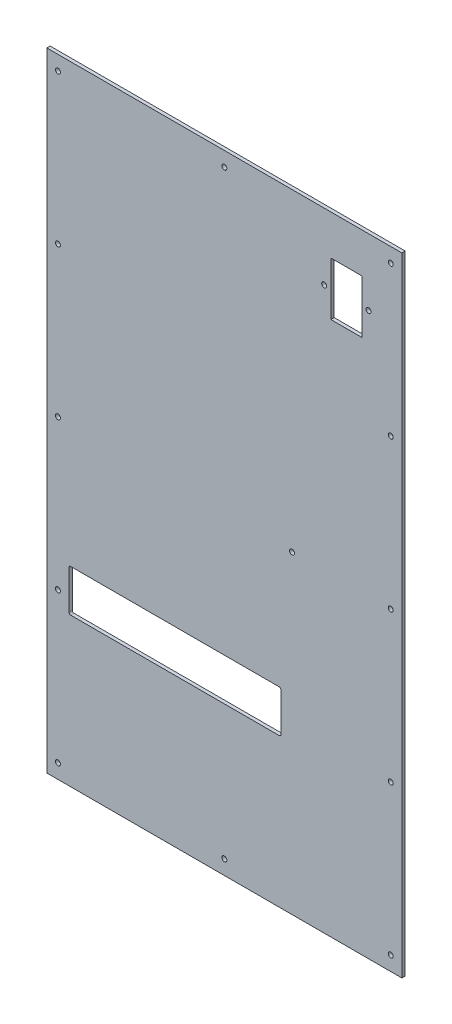
SolidWorks part; units mm, degrees
ref_plane "Спереди" through (0, 0, 0) normal (0, 0, 1) x (1, 0, 0)
ref_plane "Сверху" through (0, 0, 0) normal (0, 1, 0) x (1, 0, 0)
ref_plane "Справа" through (0, 0, 0) normal (1, 0, 0) x (0, 0, -1)
sketch "Эскиз1" plane through (0, 0, 0) normal (0, 0, 1) x (1, 0, 0)
  line L0 (0, 0) -> (320, 0)
  line L1 (0, 0) -> (0, 566)
  line L2 (320, 0) -> (320, 566)
  line L3 (0, 566) -> (320, 566)
  line L4 (10, 553) -> (310, 553) construction
  line L5 (10, 553) -> (10, 13) construction
  line L6 (310, 553) -> (310, 13) construction
  line L7 (10, 13) -> (310, 13) construction
  line L8 (160, 553) -> (160, 13) construction
  circle A0 centre (10, 553) radius 2.25
  circle A1 centre (10, 418) radius 2.25
  circle A2 centre (10, 283) radius 2.25
  circle A3 centre (10, 148) radius 2.25
  circle A4 centre (10, 13) radius 2.25
  circle A5 centre (310, 13) radius 2.25
  circle A6 centre (160, 553) radius 2.25
  circle A7 centre (310, 553) radius 2.25
  circle A8 centre (310, 418) radius 2.25
  circle A9 centre (310, 283) radius 2.25
  circle A10 centre (310, 148) radius 2.25
  circle A11 centre (160, 13) radius 2.25
  dimension "D7" = 4.5
  dimension "D9" = 135
  dimension "D10" = 4.5
  dimension "D12" = 135
  dimension "D13" = 4.5
  dimension "D14" = 4.5
  dimension "D1" = 566
  dimension "D2" = 320
  dimension "D3" = 10
  dimension "D4" = 13
  dimension "D5" = 10
  dimension "D6" = 13
  dimension "D8" = 5
  dimension "D11" = 5
extrude "Бобышка-Вытянуть1" add sketch "Эскиз1" along normal blind 3
sketch "Эскиз2" plane through (0, 0, 0) normal (0, 0, -1) x (-1, 0, 0)
  line L0 (-34.5, 497.8788) -> (-34.5, 452.1212) construction
  line L1 (-50.3712, 513.75) -> (-96.1288, 513.75) construction
  line L2 (-50.3712, 436.25) -> (-96.1288, 436.25) construction
  line L3 (-112, 497.8788) -> (-112, 452.1212) construction
  line L4 (-34.5, 497.8788) -> (-34.5, 452.1212) construction
  line L5 (-50.3712, 513.75) -> (-96.1288, 513.75) construction
  line L6 (-50.3712, 436.25) -> (-96.1288, 436.25) construction
  line L7 (-112, 497.8788) -> (-112, 452.1212) construction
  line L8 (-155.25, 500.5) -> (-124.75, 500.5) construction
  line L9 (-124.75, 475.5) -> (-155.25, 475.5) construction
  line L10 (-155.25, 500.5) -> (-124.75, 500.5) construction
  line L11 (-124.75, 475.5) -> (-155.25, 475.5) construction
  line L16 (-130, 446) -> (-130, 461)
  line L17 (-151, 446) -> (-130, 446)
  line L18 (-151, 461) -> (-151, 446)
  line L19 (-130, 461) -> (-151, 461)
  line L20 (-130, 446) -> (-130, 461) construction
  line L21 (-151, 446) -> (-130, 446) construction
  line L22 (-151, 461) -> (-151, 446) construction
  line L23 (-130, 461) -> (-151, 461) construction
  line L24 (-50.3712, 513.75) -> (-149.75, 513.75)
  line L25 (-149.75, 513.75) -> (-167.5, 496)
  line L26 (-167.5, 496) -> (-167.5, 454)
  line L27 (-157.5, 444) -> (-112.25, 444)
  line L28 (-112.25, 444) -> (-104.5, 436.25)
  line L29 (-104.5, 436.25) -> (-50.3712, 436.25)
  line L30 (-34.5, 452.1212) -> (-34.5, 497.8788)
  line L31 (-167.5, 454) -> (-157.5, 444)
  line L32 (-50.3712, 513.75) -> (-34.5, 497.8788)
  line L33 (-34.5, 452.1212) -> (-50.3712, 436.25)
  arc A0 (-50.3712, 436.25) -> (-34.5, 452.1212) centre (-73.25, 475) ccw construction
  arc A1 (-34.5, 497.8788) -> (-50.3712, 513.75) centre (-73.25, 475) ccw construction
  arc A2 (-112, 452.1212) -> (-96.1288, 436.25) centre (-73.25, 475) ccw construction
  arc A3 (-96.1288, 513.75) -> (-112, 497.8788) centre (-73.25, 475) ccw construction
  arc A4 (-50.3712, 436.25) -> (-34.5, 452.1212) centre (-73.25, 475) ccw construction
  arc A5 (-34.5, 497.8788) -> (-50.3712, 513.75) centre (-73.25, 475) ccw construction
  arc A6 (-112, 452.1212) -> (-96.1288, 436.25) centre (-73.25, 475) ccw construction
  arc A7 (-96.1288, 513.75) -> (-112, 497.8788) centre (-73.25, 475) ccw construction
  arc A8 (-124.75, 475.5) -> (-124.75, 500.5) centre (-127.8878, 488) ccw construction
  arc A9 (-155.25, 500.5) -> (-155.25, 475.5) centre (-152.1122, 488) ccw construction
  arc A10 (-124.75, 475.5) -> (-124.75, 500.5) centre (-127.8878, 488) ccw construction
  arc A11 (-155.25, 500.5) -> (-155.25, 475.5) centre (-152.1122, 488) ccw construction
  circle A12 centre (-164, 511) radius 2.25 construction
  circle A13 centre (-164, 511) radius 2.25 construction
  circle A14 centre (-140.5, 437.5) radius 2.25 construction
  circle A15 centre (-140.5, 437.5) radius 2.25 construction
  circle A16 centre (-26, 447) radius 2.25 construction
  circle A17 centre (-26, 447) radius 2.25 construction
  circle A18 centre (-26, 511) radius 2.25 construction
  circle A19 centre (-26, 511) radius 2.25 construction
  circle A20 centre (-26, 511) radius 2
  circle A21 centre (-26, 447) radius 2
  circle A22 centre (-164, 511) radius 2
  circle A23 centre (-140.5, 437.5) radius 2
  point P35 (-167.5, 444)
  dimension "D8" = 4
  dimension "D9" = 4
  dimension "D10" = 4
  dimension "D11" = 4
  dimension "D2" = 135
  dimension "D3" = 135
  dimension "D4" = 2
  dimension "D5" = 52
  dimension "D6" = 70
  dimension "D7" = 133
  dimension "D12" = 135
  dimension "D13" = 135
  dimension "D1" = 0
sketch "Эскиз3" plane through (0, 0, 0) normal (0, 0, -1) x (-1, 0, 0)
  line L0 (0, 0) -> (-320, 0) construction
  line L1 (0, 566) -> (0, 0) construction
  line L8 (-20, 134) -> (-20, 172)
  line L9 (-211, 134) -> (-20, 134)
  line L10 (-211, 172) -> (-211, 134)
  line L11 (-20, 172) -> (-211, 172)
  dimension "D1" = 172
  dimension "D6" = 38
  dimension "D7" = 20
  dimension "D8" = 191
extrude "Вырез-Вытянуть2" cut sketch "Эскиз3" against normal through all
sketch "Sketch3" plane through (0, 0, 0) normal (0, 0, -1) x (-1, 0, 0)
  line L0 (-20, 173) -> (-182, 173) construction
  line L1 (-20, 173) -> (-182, 173) construction
  line L2 (-202, 23) -> (-202, 543) construction
  line L3 (-202, 23) -> (-202, 543) construction
  line L4 (-221, 312.4311) -> (-221, 163) construction
  line L5 (-101, 153) -> (-101, 178.2817) construction
  line L6 (-211, 172) -> (-211, 134) construction
  line L8 (-20, 134) -> (-20, 172) construction
  line L9 (-202, 283) -> (-221, 283) construction
  circle A0 centre (-101, 163) radius 2.25
  circle A2 centre (-221, 283) radius 2.25
  dimension "D1" = 4.5
  dimension "D7" = 4.5
  dimension "D2" = 10
  dimension "D5" = 81
  dimension "D6" = 10
extrude "Cut-Extrude1" cut sketch "Sketch3" against normal through all
sketch "Эскиз4" plane through (0, 0, 3) normal (0, 0, 1) x (1, 0, 0)
  line L0 (256, 530) -> (284, 530)
  line L1 (256, 530) -> (256, 482)
  line L2 (284, 530) -> (284, 482)
  line L3 (256, 482) -> (284, 482)
  line L4 (270, 530) -> (270, 482) construction
  line L5 (256, 506) -> (284, 506) construction
  line L6 (320, 0) -> (320, 566) construction
  line L7 (320, 566) -> (0, 566) construction
  line L8 (250, 506) -> (290, 506) construction
  circle A0 centre (250, 506) radius 2.25
  circle A1 centre (290, 506) radius 2.25
  dimension "D7" = 4.5
  dimension "D1" = 48
  dimension "D2" = 28
  dimension "D3" = 50
  dimension "D4" = 60
  dimension "D5" = 40
  dimension "D6" = 20
extrude "Вырез-Вытянуть3" cut sketch "Эскиз4" against normal through all
fillet "Скругление1" radius 1.5 4 edges at (211, 134, 1.5) (211, 172, 1.5) (20, 134, 1.5) (20, 172, 1.5)
